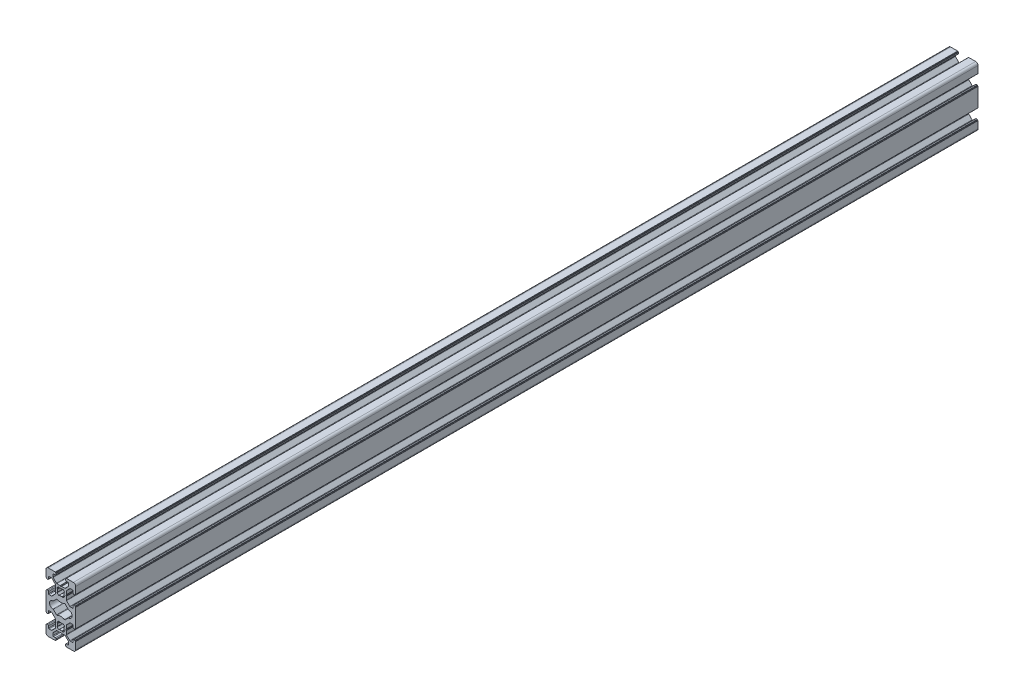
SolidWorks part; units mm, degrees
ref_plane "Front Plane-end prof " through (0, 0, 0) normal (0, 0, 1) x (1, 0, 0)
ref_plane "Top Plane-nar cl" through (0, 0, 0) normal (0, 1, 0) x (1, 0, 0)
ref_plane "Right Plane-wide cl" through (0, 0, 0) normal (1, 0, 0) x (0, 0, -1)
sketch "Sketch1" plane through (0, 0, 0) normal (0, 0, 1) x (1, 0, 0)
  line L0 (0, -7.5565) -> (0, 7.5565) construction
  line L1 (7.5565, 0) -> (-7.5565, 0) construction
  line L2 (-10.6995, -25.3987) -> (-4.7498, -25.3987)
  line L3 (4.7498, -25.3987) -> (10.6995, -25.3987)
  line L4 (-4.3498, -24.8987) -> (-4.2498, -24.8987)
  line L5 (4.2498, -24.8987) -> (4.3498, -24.8987)
  line L6 (6.2497, -23.1988) -> (4.6498, -23.1988)
  line L7 (-4.6498, -23.1988) -> (-6.2497, -23.1988)
  line L8 (-8.0174, -19.449) -> (-9.9995, -19.449)
  line L9 (8.0174, -19.449) -> (9.9995, -19.449)
  line L10 (-3.4321, -17.3991) -> (-0.6268, -17.3991)
  line L11 (0.6268, -17.3991) -> (3.4321, -17.3991)
  line L12 (-12.3994, -17.2491) -> (-12.4994, -17.2491)
  line L13 (12.3994, -17.2491) -> (12.4994, -17.2491)
  line L14 (-11.0994, -16.7491) -> (-11.9994, -16.7491)
  line L15 (11.0994, -16.7491) -> (11.9994, -16.7491)
  line L16 (0.1, 17.1259) -> (0.5268, 17.3723)
  line L17 (0.1, -17.1259) -> (0.5268, -17.3723)
  line L18 (-12.6993, 23.3988) -> (-12.6993, 17.4491)
  line L19 (-12.6993, 7.9496) -> (-12.6993, -7.9496)
  line L20 (-12.6993, -17.4491) -> (-12.6993, -23.3988)
  line L21 (-12.1994, 17.0491) -> (-12.1994, 16.9491)
  line L22 (-12.1994, 8.4496) -> (-12.1994, 8.3496)
  line L23 (-12.1994, -8.3496) -> (-12.1994, -8.4496)
  line L24 (-12.1994, -16.9491) -> (-12.1994, -17.0491)
  line L25 (-2.7718, 11.4069) -> (-2.9783, 11.3106)
  line L26 (2.7718, 13.9918) -> (2.9783, 14.0881)
  line L27 (0, -12.6993) -> (-1.2725, -12.6993) construction
  line L28 (0, -12.6993) -> (1.2725, -12.6993) construction
  line L29 (-2.9783, -11.3106) -> (-2.7718, -11.4069)
  line L30 (2.9783, -14.0881) -> (2.7718, -13.9918)
  line L31 (-10.4995, -18.949) -> (-10.4995, -17.3491)
  line L32 (-10.4995, -8.0496) -> (-10.4995, -6.4497)
  line L33 (-10.4995, 6.4497) -> (-10.4995, 8.0496)
  line L34 (-10.4995, 17.3491) -> (-10.4995, 18.949)
  line L35 (-4.4266, 12.5994) -> (-4.673, 12.1726)
  line L36 (-4.8462, 8.9138) -> (-7.6638, 6.0961)
  line L37 (3.7856, 17.5455) -> (6.6032, 20.3632)
  line L38 (-7.6638, -6.0961) -> (-4.8462, -8.9138)
  line L39 (3.7856, -17.5455) -> (6.6032, -20.3632)
  line L40 (-4.673, -12.1726) -> (-4.4266, -12.5994)
  line L41 (7.6638, 19.3026) -> (4.8462, 16.4849)
  line L42 (11.9994, -8.6496) -> (11.0994, -8.6496)
  line L43 (-11.9994, -8.6496) -> (-11.0994, -8.6496)
  line L44 (12.4994, -8.1496) -> (12.3994, -8.1496)
  line L45 (-12.4994, -8.1496) -> (-12.3994, -8.1496)
  line L46 (4.8462, -16.4849) -> (7.6638, -19.3026)
  line L47 (-6.7497, 22.6988) -> (-6.7497, 20.7167)
  line L48 (-6.7497, -22.6988) -> (-6.7497, -20.7167)
  line L49 (-3.721, 5.7966) -> (-6.3713, 3.1462)
  line L50 (9.9995, -5.9497) -> (8.0174, -5.9497)
  line L51 (-9.9995, -5.9497) -> (-8.0174, -5.9497)
  line L52 (-6.3713, -3.1462) -> (-3.721, -5.7966)
  line L53 (-4.6998, 16.1314) -> (-4.6998, 13.3261)
  line L54 (-4.6998, 12.0726) -> (-4.6998, 9.2673)
  line L55 (-4.6998, -9.2673) -> (-4.6998, -12.0726)
  line L56 (-4.6998, -13.3261) -> (-4.6998, -16.1314)
  line L57 (-4.5498, 25.1987) -> (-4.5498, 25.0987)
  line L58 (-4.5498, -25.1987) -> (-4.5498, -25.0987)
  line L59 (-4.0498, 24.6987) -> (-4.0498, 23.7988)
  line L60 (-4.0498, -24.6987) -> (-4.0498, -23.7988)
  line L61 (1.3888, 15.6776) -> (1.2925, 15.4711)
  line L62 (-1.3888, 9.7211) -> (-1.2925, 9.9276)
  line L63 (1.2925, -15.4711) -> (1.3888, -15.6776)
  line L64 (-1.2925, -9.9276) -> (-1.3888, -9.7211)
  line L65 (4.673, 13.2261) -> (4.4266, 12.7993)
  line L66 (4.4266, -12.7993) -> (4.673, -13.2261)
  line L67 (0, 12.6993) -> (0, 11.4268) construction
  line L68 (0, -12.6993) -> (0, -13.9719) construction
  line L69 (0, -12.6993) -> (0, -11.4268) construction
  line L70 (0, 12.6993) -> (0, 13.9719) construction
  line L71 (-4.4266, -12.7993) -> (-4.673, -13.2261)
  line L72 (-4.673, 13.2261) -> (-4.4266, 12.7993)
  line L73 (4.0498, -23.7988) -> (4.0498, -24.6987)
  line L74 (4.0498, 23.7988) -> (4.0498, 24.6987)
  line L75 (4.5498, -25.0987) -> (4.5498, -25.1987)
  line L76 (4.5498, 25.0987) -> (4.5498, 25.1987)
  line L77 (4.6998, 16.1314) -> (4.6998, 13.3261)
  line L78 (4.6998, 12.0726) -> (4.6998, 9.2673)
  line L79 (4.6998, -9.2673) -> (4.6998, -12.0726)
  line L80 (4.6998, -13.3261) -> (4.6998, -16.1314)
  line L81 (1.3888, -9.7211) -> (1.2925, -9.9276)
  line L82 (-1.3888, -15.6776) -> (-1.2925, -15.4711)
  line L83 (1.2925, 9.9276) -> (1.3888, 9.7211)
  line L84 (-1.2925, 15.4711) -> (-1.3888, 15.6776)
  line L85 (6.7497, -20.7167) -> (6.7497, -22.6988)
  line L86 (6.7497, 20.7167) -> (6.7497, 22.6988)
  line L87 (3.721, -5.7966) -> (6.3713, -3.1462)
  line L88 (-8.0174, 5.9497) -> (-9.9995, 5.9497)
  line L89 (8.0174, 5.9497) -> (9.9995, 5.9497)
  line L90 (6.3713, 3.1462) -> (3.721, 5.7966)
  line L91 (-4.8462, -16.4849) -> (-7.6638, -19.3026)
  line L92 (-12.3994, 8.1496) -> (-12.4994, 8.1496)
  line L93 (12.3994, 8.1496) -> (12.4994, 8.1496)
  line L94 (-11.0994, 8.6496) -> (-11.9994, 8.6496)
  line L95 (11.0994, 8.6496) -> (11.9994, 8.6496)
  line L96 (-7.6638, 19.3026) -> (-4.8462, 16.4849)
  line L97 (10.4995, -18.949) -> (10.4995, -17.3491)
  line L98 (10.4995, -8.0496) -> (10.4995, -6.4497)
  line L99 (10.4995, 6.4497) -> (10.4995, 8.0496)
  line L100 (10.4995, 17.3491) -> (10.4995, 18.949)
  line L101 (4.673, -12.1726) -> (4.4266, -12.5994)
  line L102 (7.6638, -6.0961) -> (4.8462, -8.9138)
  line L103 (-6.6032, -20.3632) -> (-3.7856, -17.5455)
  line L104 (-2.7718, -13.9918) -> (-2.9783, -14.0881)
  line L105 (2.7718, -11.4069) -> (2.9783, -11.3106)
  line L106 (-2.9783, 14.0881) -> (-2.7718, 13.9918)
  line L107 (2.9783, 11.3106) -> (2.7718, 11.4069)
  line L108 (-6.6032, 20.3632) -> (-3.7856, 17.5455)
  line L109 (4.8462, 8.9138) -> (7.6638, 6.0961)
  line L110 (4.4266, 12.5994) -> (4.673, 12.1726)
  line L111 (12.1994, 17.0491) -> (12.1994, 16.9491)
  line L112 (12.1994, 8.4496) -> (12.1994, 8.3496)
  line L113 (12.1994, -8.3496) -> (12.1994, -8.4496)
  line L114 (12.1994, -16.9491) -> (12.1994, -17.0491)
  line L115 (12.6993, -23.3988) -> (12.6993, -17.4491)
  line L116 (12.6993, -7.9496) -> (12.6993, 7.9496)
  line L117 (12.6993, 17.4491) -> (12.6993, 23.3988)
  line L118 (0, 12.6993) -> (-1.2725, 12.6993) construction
  line L119 (0, 12.6993) -> (1.2725, 12.6993) construction
  line L120 (-0.5268, -17.3723) -> (-0.1, -17.1259)
  line L121 (-0.5268, 17.3723) -> (-0.1, 17.1259)
  line L122 (11.9994, 16.7491) -> (11.0994, 16.7491)
  line L123 (-11.9994, 16.7491) -> (-11.0994, 16.7491)
  line L124 (12.4994, 17.2491) -> (12.3994, 17.2491)
  line L125 (-12.4994, 17.2491) -> (-12.3994, 17.2491)
  line L126 (-3.4321, 17.3991) -> (-0.6268, 17.3991)
  line L127 (0.6268, 17.3991) -> (3.4321, 17.3991)
  line L128 (9.9995, 19.449) -> (8.0174, 19.449)
  line L129 (-9.9995, 19.449) -> (-8.0174, 19.449)
  line L130 (6.2497, 23.1988) -> (4.6498, 23.1988)
  line L131 (-4.6498, 23.1988) -> (-6.2497, 23.1988)
  line L132 (-4.3498, 24.8987) -> (-4.2498, 24.8987)
  line L133 (4.2498, 24.8987) -> (4.3498, 24.8987)
  line L134 (10.6995, 25.3987) -> (4.7498, 25.3987)
  line L135 (-4.7498, 25.3987) -> (-10.6995, 25.3987)
  arc A0 (-4.7498, -25.3987) -> (-4.5498, -25.1987) centre (-4.7498, -25.1987) ccw
  arc A1 (-12.6993, -23.3988) -> (-10.6995, -25.3987) centre (-10.6995, -23.3988) ccw
  arc A2 (-12.4994, -17.2491) -> (-12.6993, -17.4491) centre (-12.4994, -17.4491) ccw
  arc A3 (-12.3994, -17.2491) -> (-12.1994, -17.0491) centre (-12.3994, -17.0491) ccw
  arc A4 (-11.9994, -16.7491) -> (-12.1994, -16.9491) centre (-11.9994, -16.9491) ccw
  arc A5 (-10.4995, -17.3491) -> (-11.0994, -16.7491) centre (-11.0994, -17.3491) ccw
  arc A6 (-10.4995, -18.949) -> (-9.9995, -19.449) centre (-9.9995, -18.949) ccw
  arc A7 (-8.0174, -19.449) -> (-7.6638, -19.3026) centre (-8.0174, -18.949) ccw
  arc A8 (-4.8462, -16.4849) -> (-4.6998, -16.1314) centre (-5.1997, -16.1314) ccw
  arc A9 (-4.673, -13.2261) -> (-4.6998, -13.3261) centre (-4.4998, -13.3261) ccw
  arc A10 (-4.4266, -12.7993) -> (-4.4266, -12.5994) centre (-4.5998, -12.6993) ccw
  arc A11 (-4.6998, -12.0726) -> (-4.673, -12.1726) centre (-4.4998, -12.0726) ccw
  arc A12 (-4.6998, -9.2673) -> (-4.8462, -8.9138) centre (-5.1997, -9.2673) ccw
  arc A13 (-7.6638, -6.0961) -> (-8.0174, -5.9497) centre (-8.0174, -6.4497) ccw
  arc A14 (-9.9995, -5.9497) -> (-10.4995, -6.4497) centre (-9.9995, -6.4497) ccw
  arc A15 (-11.0994, -8.6496) -> (-10.4995, -8.0496) centre (-11.0994, -8.0496) ccw
  arc A16 (-12.1994, -8.4496) -> (-11.9994, -8.6496) centre (-11.9994, -8.4496) ccw
  arc A17 (-12.1994, -8.3496) -> (-12.3994, -8.1496) centre (-12.3994, -8.3496) ccw
  arc A18 (-12.6993, -7.9496) -> (-12.4994, -8.1496) centre (-12.4994, -7.9496) ccw
  arc A19 (-12.4994, 8.1496) -> (-12.6993, 7.9496) centre (-12.4994, 7.9496) ccw
  arc A20 (-12.3994, 8.1496) -> (-12.1994, 8.3496) centre (-12.3994, 8.3496) ccw
  arc A21 (-11.9994, 8.6496) -> (-12.1994, 8.4496) centre (-11.9994, 8.4496) ccw
  arc A22 (-10.4995, 8.0496) -> (-11.0994, 8.6496) centre (-11.0994, 8.0496) ccw
  arc A23 (-10.4995, 6.4497) -> (-9.9995, 5.9497) centre (-9.9995, 6.4497) ccw
  arc A24 (-8.0174, 5.9497) -> (-7.6638, 6.0961) centre (-8.0174, 6.4497) ccw
  arc A25 (-4.8462, 8.9138) -> (-4.6998, 9.2673) centre (-5.1997, 9.2673) ccw
  arc A26 (-4.673, 12.1726) -> (-4.6998, 12.0726) centre (-4.4998, 12.0726) ccw
  arc A27 (-4.4266, 12.5994) -> (-4.4266, 12.7993) centre (-4.5998, 12.6993) ccw
  arc A28 (-4.6998, 13.3261) -> (-4.673, 13.2261) centre (-4.4998, 13.3261) ccw
  arc A29 (-4.6998, 16.1314) -> (-4.8462, 16.4849) centre (-5.1997, 16.1314) ccw
  arc A30 (-7.6638, 19.3026) -> (-8.0174, 19.449) centre (-8.0174, 18.949) ccw
  arc A31 (-9.9995, 19.449) -> (-10.4995, 18.949) centre (-9.9995, 18.949) ccw
  arc A32 (-11.0994, 16.7491) -> (-10.4995, 17.3491) centre (-11.0994, 17.3491) ccw
  arc A33 (-12.1994, 16.9491) -> (-11.9994, 16.7491) centre (-11.9994, 16.9491) ccw
  arc A34 (-12.1994, 17.0491) -> (-12.3994, 17.2491) centre (-12.3994, 17.0491) ccw
  arc A35 (-12.6993, 17.4491) -> (-12.4994, 17.2491) centre (-12.4994, 17.4491) ccw
  arc A36 (-10.6995, 25.3987) -> (-12.6993, 23.3988) centre (-10.6995, 23.3988) ccw
  arc A37 (-4.5498, 25.1987) -> (-4.7498, 25.3987) centre (-4.7498, 25.1987) ccw
  arc A38 (-4.5498, 25.0987) -> (-4.3498, 24.8987) centre (-4.3498, 25.0987) ccw
  arc A39 (-4.0498, 24.6987) -> (-4.2498, 24.8987) centre (-4.2498, 24.6987) ccw
  arc A40 (-4.6498, 23.1988) -> (-4.0498, 23.7988) centre (-4.6498, 23.7988) ccw
  arc A41 (-6.2497, 23.1988) -> (-6.7497, 22.6988) centre (-6.2497, 22.6988) ccw
  arc A42 (-6.7497, 20.7167) -> (-6.6032, 20.3632) centre (-6.2497, 20.7167) ccw
  arc A43 (-3.7856, 17.5455) -> (-3.4321, 17.3991) centre (-3.4321, 17.8991) ccw
  arc A44 (-0.5268, 17.3723) -> (-0.6268, 17.3991) centre (-0.6268, 17.1991) ccw
  arc A45 (-0.1, 17.1259) -> (0.1, 17.1259) centre (0, 17.2991) ccw
  arc A46 (0.6268, 17.3991) -> (0.5268, 17.3723) centre (0.6268, 17.1991) ccw
  arc A47 (3.4321, 17.3991) -> (3.7856, 17.5455) centre (3.4321, 17.8991) ccw
  arc A48 (6.6032, 20.3632) -> (6.7497, 20.7167) centre (6.2497, 20.7167) ccw
  arc A49 (6.7497, 22.6988) -> (6.2497, 23.1988) centre (6.2497, 22.6988) ccw
  arc A50 (4.0498, 23.7988) -> (4.6498, 23.1988) centre (4.6498, 23.7988) ccw
  arc A51 (4.2498, 24.8987) -> (4.0498, 24.6987) centre (4.2498, 24.6987) ccw
  arc A52 (4.3498, 24.8987) -> (4.5498, 25.0987) centre (4.3498, 25.0987) ccw
  arc A53 (4.7498, 25.3987) -> (4.5498, 25.1987) centre (4.7498, 25.1987) ccw
  arc A54 (12.6993, 23.3988) -> (10.6995, 25.3987) centre (10.6995, 23.3988) ccw
  arc A55 (12.4994, 17.2491) -> (12.6993, 17.4491) centre (12.4994, 17.4491) ccw
  arc A56 (12.3994, 17.2491) -> (12.1994, 17.0491) centre (12.3994, 17.0491) ccw
  arc A57 (11.9994, 16.7491) -> (12.1994, 16.9491) centre (11.9994, 16.9491) ccw
  arc A58 (10.4995, 17.3491) -> (11.0994, 16.7491) centre (11.0994, 17.3491) ccw
  arc A59 (10.4995, 18.949) -> (9.9995, 19.449) centre (9.9995, 18.949) ccw
  arc A60 (8.0174, 19.449) -> (7.6638, 19.3026) centre (8.0174, 18.949) ccw
  arc A61 (4.8462, 16.4849) -> (4.6998, 16.1314) centre (5.1997, 16.1314) ccw
  arc A62 (4.673, 13.2261) -> (4.6998, 13.3261) centre (4.4998, 13.3261) ccw
  arc A63 (4.4266, 12.7993) -> (4.4266, 12.5994) centre (4.5998, 12.6993) ccw
  arc A64 (4.6998, 12.0726) -> (4.673, 12.1726) centre (4.4998, 12.0726) ccw
  arc A65 (4.6998, 9.2673) -> (4.8462, 8.9138) centre (5.1997, 9.2673) ccw
  arc A66 (7.6638, 6.0961) -> (8.0174, 5.9497) centre (8.0174, 6.4497) ccw
  arc A67 (9.9995, 5.9497) -> (10.4995, 6.4497) centre (9.9995, 6.4497) ccw
  arc A68 (11.0994, 8.6496) -> (10.4995, 8.0496) centre (11.0994, 8.0496) ccw
  arc A69 (12.1994, 8.4496) -> (11.9994, 8.6496) centre (11.9994, 8.4496) ccw
  arc A70 (12.1994, 8.3496) -> (12.3994, 8.1496) centre (12.3994, 8.3496) ccw
  arc A71 (12.6993, 7.9496) -> (12.4994, 8.1496) centre (12.4994, 7.9496) ccw
  arc A72 (12.4994, -8.1496) -> (12.6993, -7.9496) centre (12.4994, -7.9496) ccw
  arc A73 (12.3994, -8.1496) -> (12.1994, -8.3496) centre (12.3994, -8.3496) ccw
  arc A74 (11.9994, -8.6496) -> (12.1994, -8.4496) centre (11.9994, -8.4496) ccw
  arc A75 (10.4995, -8.0496) -> (11.0994, -8.6496) centre (11.0994, -8.0496) ccw
  arc A76 (10.4995, -6.4497) -> (9.9995, -5.9497) centre (9.9995, -6.4497) ccw
  arc A77 (8.0174, -5.9497) -> (7.6638, -6.0961) centre (8.0174, -6.4497) ccw
  arc A78 (4.8462, -8.9138) -> (4.6998, -9.2673) centre (5.1997, -9.2673) ccw
  arc A79 (4.673, -12.1726) -> (4.6998, -12.0726) centre (4.4998, -12.0726) ccw
  arc A80 (4.4266, -12.5994) -> (4.4266, -12.7993) centre (4.5998, -12.6993) ccw
  arc A81 (4.6998, -13.3261) -> (4.673, -13.2261) centre (4.4998, -13.3261) ccw
  arc A82 (4.6998, -16.1314) -> (4.8462, -16.4849) centre (5.1997, -16.1314) ccw
  arc A83 (7.6638, -19.3026) -> (8.0174, -19.449) centre (8.0174, -18.949) ccw
  arc A84 (9.9995, -19.449) -> (10.4995, -18.949) centre (9.9995, -18.949) ccw
  arc A85 (11.0994, -16.7491) -> (10.4995, -17.3491) centre (11.0994, -17.3491) ccw
  arc A86 (12.1994, -16.9491) -> (11.9994, -16.7491) centre (11.9994, -16.9491) ccw
  arc A87 (12.1994, -17.0491) -> (12.3994, -17.2491) centre (12.3994, -17.0491) ccw
  arc A88 (12.6993, -17.4491) -> (12.4994, -17.2491) centre (12.4994, -17.4491) ccw
  arc A89 (10.6995, -25.3987) -> (12.6993, -23.3988) centre (10.6995, -23.3988) ccw
  arc A90 (4.5498, -25.1987) -> (4.7498, -25.3987) centre (4.7498, -25.1987) ccw
  arc A91 (4.5498, -25.0987) -> (4.3498, -24.8987) centre (4.3498, -25.0987) ccw
  arc A92 (4.0498, -24.6987) -> (4.2498, -24.8987) centre (4.2498, -24.6987) ccw
  arc A93 (4.6498, -23.1988) -> (4.0498, -23.7988) centre (4.6498, -23.7988) ccw
  arc A94 (6.2497, -23.1988) -> (6.7497, -22.6988) centre (6.2497, -22.6988) ccw
  arc A95 (6.7497, -20.7167) -> (6.6032, -20.3632) centre (6.2497, -20.7167) ccw
  arc A96 (3.7856, -17.5455) -> (3.4321, -17.3991) centre (3.4321, -17.8991) ccw
  arc A97 (0.5268, -17.3723) -> (0.6268, -17.3991) centre (0.6268, -17.1991) ccw
  arc A98 (0.1, -17.1259) -> (-0.1, -17.1259) centre (0, -17.2991) ccw
  arc A99 (-0.6268, -17.3991) -> (-0.5268, -17.3723) centre (-0.6268, -17.1991) ccw
  arc A100 (-3.4321, -17.3991) -> (-3.7856, -17.5455) centre (-3.4321, -17.8991) ccw
  arc A101 (-6.6032, -20.3632) -> (-6.7497, -20.7167) centre (-6.2497, -20.7167) ccw
  arc A102 (-6.7497, -22.6988) -> (-6.2497, -23.1988) centre (-6.2497, -22.6988) ccw
  arc A103 (-4.0498, -23.7988) -> (-4.6498, -23.1988) centre (-4.6498, -23.7988) ccw
  arc A104 (-4.2498, -24.8987) -> (-4.0498, -24.6987) centre (-4.2498, -24.6987) ccw
  arc A105 (-4.3498, -24.8987) -> (-4.5498, -25.0987) centre (-4.3498, -25.0987) ccw
  arc A106 (6.7213, -2.9998) -> (6.7213, 2.9998) centre (6.6997, 0) ccw
  arc A107 (6.3713, 3.1462) -> (6.7213, 2.9998) centre (6.7249, 3.4997) ccw
  arc A108 (3.721, 5.7966) -> (3.157, 5.8966) centre (3.3674, 5.443) ccw
  arc A109 (-3.157, 5.8966) -> (3.157, 5.8966) centre (0, 12.6993) ccw
  arc A110 (-3.157, 5.8966) -> (-3.721, 5.7966) centre (-3.3674, 5.443) ccw
  arc A111 (-6.7213, 2.9998) -> (-6.3713, 3.1462) centre (-6.7249, 3.4997) ccw
  arc A112 (-6.7213, 2.9998) -> (-6.7213, -2.9998) centre (-6.6997, 0) ccw
  arc A113 (-6.3713, -3.1462) -> (-6.7213, -2.9998) centre (-6.7249, -3.4997) ccw
  arc A114 (-3.721, -5.7966) -> (-3.157, -5.8966) centre (-3.3674, -5.443) ccw
  arc A115 (3.157, -5.8966) -> (-3.157, -5.8966) centre (0, -12.6993) ccw
  arc A116 (3.157, -5.8966) -> (3.721, -5.7966) centre (3.3674, -5.443) ccw
  arc A117 (6.7213, -2.9998) -> (6.3713, -3.1462) centre (6.7249, -3.4997) ccw
  arc A118 (-1.0387, 10.0294) -> (1.0387, 10.0294) centre (0, 12.6993) ccw
  arc A119 (1.2925, 9.9276) -> (1.0387, 10.0294) centre (1.1112, 9.8431) ccw
  arc A120 (1.3888, 9.7211) -> (1.8116, 9.5886) centre (1.6607, 9.8478) ccw
  arc A121 (1.8116, 9.5886) -> (3.1107, 10.8877) centre (0, 12.6993) ccw
  arc A122 (3.1107, 10.8877) -> (2.9783, 11.3106) centre (2.8515, 11.0387) ccw
  arc A123 (2.6699, 11.6606) -> (2.7718, 11.4069) centre (2.8563, 11.5881) ccw
  arc A124 (2.6699, 11.6606) -> (2.6699, 13.7381) centre (0, 12.6993) ccw
  arc A125 (2.7718, 13.9918) -> (2.6699, 13.7381) centre (2.8563, 13.8106) ccw
  arc A126 (2.9783, 14.0881) -> (3.1107, 14.511) centre (2.8515, 14.36) ccw
  arc A127 (3.1107, 14.511) -> (1.8116, 15.8101) centre (0, 12.6993) ccw
  arc A128 (1.8116, 15.8101) -> (1.3888, 15.6776) centre (1.6607, 15.5508) ccw
  arc A129 (1.0387, 15.3693) -> (1.2925, 15.4711) centre (1.1112, 15.5556) ccw
  arc A130 (1.0387, 15.3693) -> (-1.0387, 15.3693) centre (0, 12.6993) ccw
  arc A131 (-1.2925, 15.4711) -> (-1.0387, 15.3693) centre (-1.1112, 15.5556) ccw
  arc A132 (-1.3888, 15.6776) -> (-1.8116, 15.8101) centre (-1.6607, 15.5508) ccw
  arc A133 (-1.8116, 15.8101) -> (-3.1107, 14.511) centre (0, 12.6993) ccw
  arc A134 (-3.1107, 14.511) -> (-2.9783, 14.0881) centre (-2.8515, 14.36) ccw
  arc A135 (-2.6699, 13.7381) -> (-2.7718, 13.9918) centre (-2.8563, 13.8106) ccw
  arc A136 (-2.6699, 13.7381) -> (-2.6699, 11.6606) centre (0, 12.6993) ccw
  arc A137 (-2.7718, 11.4069) -> (-2.6699, 11.6606) centre (-2.8563, 11.5881) ccw
  arc A138 (-2.9783, 11.3106) -> (-3.1107, 10.8877) centre (-2.8515, 11.0387) ccw
  arc A139 (-3.1107, 10.8877) -> (-1.8116, 9.5886) centre (0, 12.6993) ccw
  arc A140 (-1.8116, 9.5886) -> (-1.3888, 9.7211) centre (-1.6607, 9.8478) ccw
  arc A141 (-1.0387, 10.0294) -> (-1.2925, 9.9276) centre (-1.1112, 9.8431) ccw
  arc A142 (2.6699, -13.7381) -> (2.6699, -11.6606) centre (0, -12.6993) ccw
  arc A143 (2.7718, -11.4069) -> (2.6699, -11.6606) centre (2.8563, -11.5881) ccw
  arc A144 (2.9783, -11.3106) -> (3.1107, -10.8877) centre (2.8515, -11.0387) ccw
  arc A145 (3.1107, -10.8877) -> (1.8116, -9.5886) centre (0, -12.6993) ccw
  arc A146 (1.8116, -9.5886) -> (1.3888, -9.7211) centre (1.6607, -9.8478) ccw
  arc A147 (1.0387, -10.0294) -> (1.2925, -9.9276) centre (1.1112, -9.8431) ccw
  arc A148 (1.0387, -10.0294) -> (-1.0387, -10.0294) centre (0, -12.6993) ccw
  arc A149 (-1.2925, -9.9276) -> (-1.0387, -10.0294) centre (-1.1112, -9.8431) ccw
  arc A150 (-1.3888, -9.7211) -> (-1.8116, -9.5886) centre (-1.6607, -9.8478) ccw
  arc A151 (-1.8116, -9.5886) -> (-3.1107, -10.8877) centre (0, -12.6993) ccw
  arc A152 (-3.1107, -10.8877) -> (-2.9783, -11.3106) centre (-2.8515, -11.0387) ccw
  arc A153 (-2.6699, -11.6606) -> (-2.7718, -11.4069) centre (-2.8563, -11.5881) ccw
  arc A154 (-2.6699, -11.6606) -> (-2.6699, -13.7381) centre (0, -12.6993) ccw
  arc A155 (-2.7718, -13.9918) -> (-2.6699, -13.7381) centre (-2.8563, -13.8106) ccw
  arc A156 (-2.9783, -14.0881) -> (-3.1107, -14.511) centre (-2.8515, -14.36) ccw
  arc A157 (-3.1107, -14.511) -> (-1.8116, -15.8101) centre (0, -12.6993) ccw
  arc A158 (-1.8116, -15.8101) -> (-1.3888, -15.6776) centre (-1.6607, -15.5508) ccw
  arc A159 (-1.0387, -15.3693) -> (-1.2925, -15.4711) centre (-1.1112, -15.5556) ccw
  arc A160 (-1.0387, -15.3693) -> (1.0387, -15.3693) centre (0, -12.6993) ccw
  arc A161 (1.2925, -15.4711) -> (1.0387, -15.3693) centre (1.1112, -15.5556) ccw
  arc A162 (1.3888, -15.6776) -> (1.8116, -15.8101) centre (1.6607, -15.5508) ccw
  arc A163 (1.8116, -15.8101) -> (3.1107, -14.511) centre (0, -12.6993) ccw
  arc A164 (3.1107, -14.511) -> (2.9783, -14.0881) centre (2.8515, -14.36) ccw
  arc A165 (2.6699, -13.7381) -> (2.7718, -13.9918) centre (2.8563, -13.8106) ccw
  point P600 (0, 0)
  dimension "D5" = 8.0996
  dimension "D7" = 5.7297
  dimension "D6" = 7.9996
  dimension "D1" = 25.3987
  dimension "D2" = 12.6993
  dimension "D3" = 25.3987
  dimension "D4" = 50.7974
extrude "Extrude1" add sketch "Sketch1" along normal mid plane 771.525
ref_axis "Axis2" through (0, 12.6993, 385.7625) along (0, 0, -1)
ref_axis "Axis3" through (0, -12.6993, 385.7625) along (0, 0, -1)
ref_plane "Plane1" through (0, 0, 0) normal (0, 0, 1) x (1, 0, 0)
sketch "Sketch2" plane through (12.6993, 0, 0) normal (1, 0, 0) x (0, 0, -1)
  line L0 (-385.7625, 25.3987) -> (385.7625, 25.3987) construction
  line L1 (385.7625, -7.9496) -> (385.7625, 7.9496) construction
  line L2 (-385.7625, 17.4491) -> (-385.7625, 23.3988) construction
  circle A0 centre (366.7125, -0.0013) radius 8.5
  circle A1 centre (-366.7125, -0.0013) radius 8.5
  dimension "D1" = 17
  dimension "D3" = 19.05
  dimension "D4" = 19.05
  dimension "D2" = 25.4
extrude "Extrude2" [suppressed] cut sketch "Sketch2" against normal through all
ref_point "Point1"
ref_plane "Plane2" through (0, 12.6993, 0) normal (0, 1, 0) x (-1, 0, 0)
ref_point "Point2"
ref_plane "Plane3" through (0, -12.6993, 0) normal (0, 1, 0) x (-1, 0, 0)
ref_plane "Plane4" through (0, 25.4, 0) normal (0, 1, 0) x (-1, 0, 0)
ref_plane "Plane5" through (0, -25.4, 0) normal (0, 1, 0) x (-1, 0, 0)
